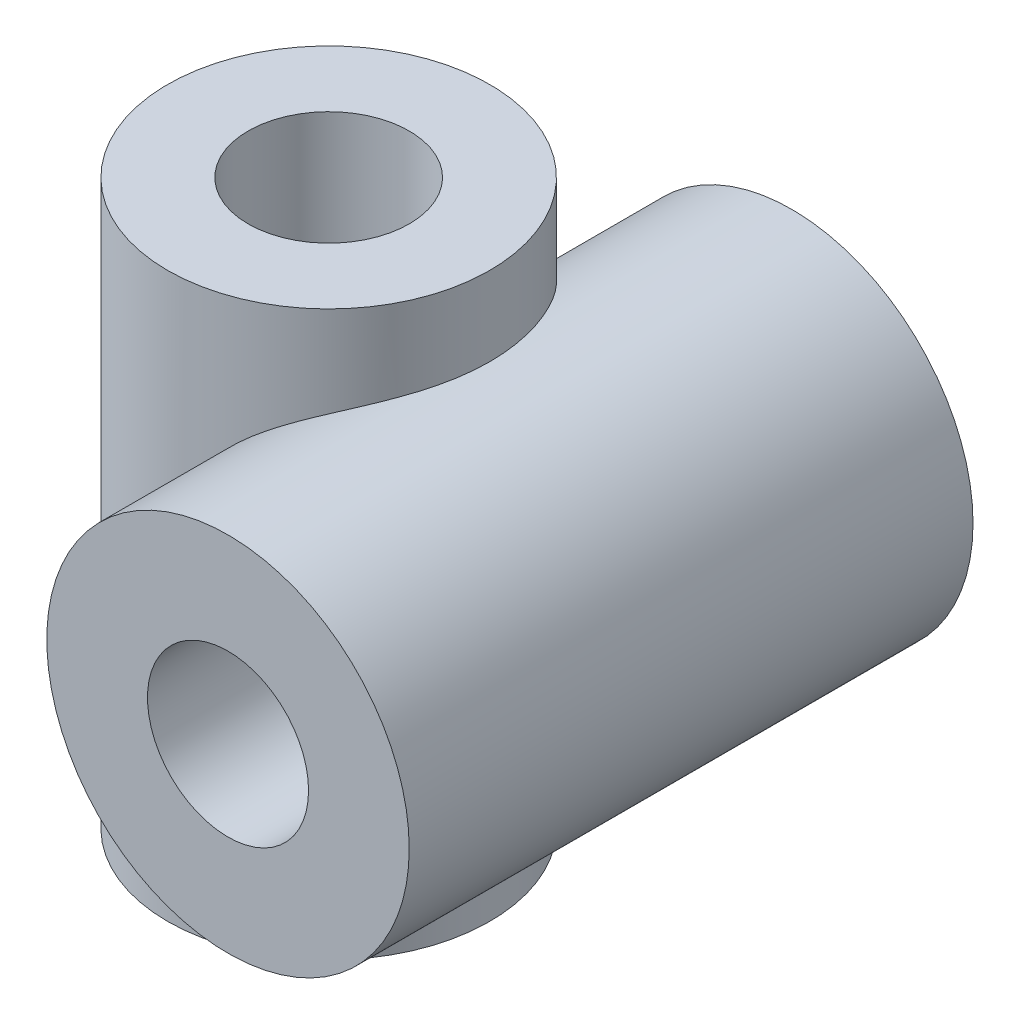
SolidWorks part; units mm, degrees
material "Gray Cast Iron"
ref_plane "Front Plane" through (0, 0, 0) normal (0, 0, 1) x (1, 0, 0)
ref_plane "Top Plane" through (0, 0, 0) normal (0, 1, 0) x (1, 0, 0)
ref_plane "Right Plane" through (0, 0, 0) normal (1, 0, 0) x (0, 0, -1)
sketch "Sketch1" plane through (0, 0, 0) normal (0, 1, 0) x (1, 0, 0)
  circle A0 centre (0, 0) radius 16
  circle A1 centre (0, 0) radius 8
extrude "Boss-Extrude1" add sketch "Sketch1" along normal blind 56
sketch "Sketch2" plane through (0, 0, 0) normal (0, 0, 1) x (1, 0, 0)
  line L0 (0, 56) -> (0, 0) construction
  circle A0 centre (18, 30.2581) radius 8
  circle A1 centre (18, 30.2581) radius 18
  dimension "D1" = 36
  dimension "D2" = 16
  dimension "D3" = 18
extrude "Boss-Extrude2" add sketch "Sketch2" along normal blind 28 and the other way blind 28
sketch "Sketch3" plane through (0, 56, 0) normal (0, 1, 0) x (1, 0, 0)
  circle A0 centre (0, 0) radius 8
extrude "Cut-Extrude1" cut sketch "Sketch3" against normal through all
sketch "Sketch4" plane through (0, 0, 28) normal (0, 0, 1) x (1, 0, 0)
  circle A0 centre (18, 30.2581) radius 8
extrude "Cut-Extrude2" cut sketch "Sketch4" against normal through all
scale "Escala1" scale about centroid uniform scaling yes scale factor 0.5
